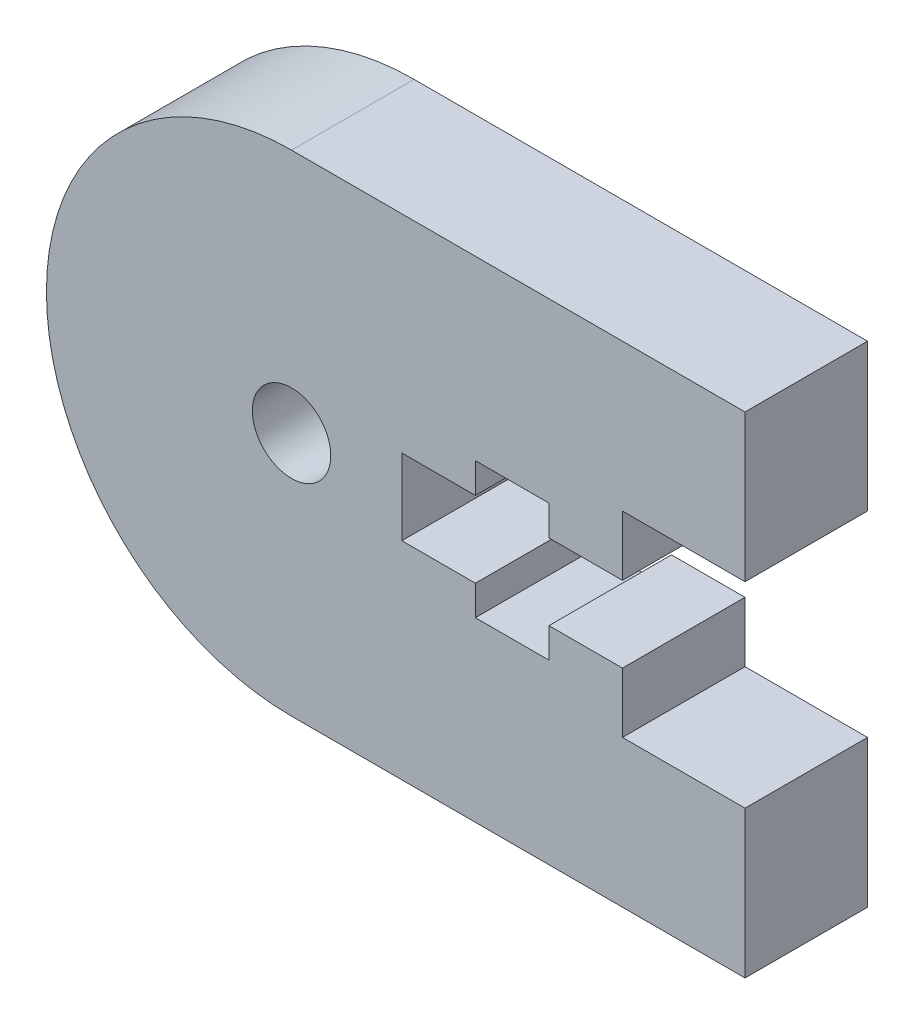
SolidWorks part; units mm, degrees
ref_plane "Plan de face" through (0, 0, 0) normal (0, 0, 1) x (1, 0, 0)
ref_plane "Plan de dessus" through (0, 0, 0) normal (0, 1, 0) x (1, 0, 0)
ref_plane "Plan de droite" through (0, 0, 0) normal (1, 0, 0) x (0, 0, -1)
ref_plane "Plan1" through (0, 0, 0) normal (0, 0, -1) x (-1, 0, 0)
sketch "Esquisse1" plane through (0, 0, 0) normal (0, 0, -1) x (-1, 0, 0)
  line L0 (-17, 10) -> (-17, -10)
  line L1 (-17, -10) -> (1.5, -10)
  line L2 (1.5, 10) -> (-17, 10)
  arc A0 (1.5, -10) -> (1.5, 10) centre (1.5, 0) ccw
  dimension "D1" = 20
extrude "Boss.-Extru.1" add sketch "Esquisse1" against normal blind 5
sketch "Esquisse2" plane through (0, 0, 5) normal (0, 0, 1) x (1, 0, 0)
  line L0 (17, -4) -> (17, 4)
  line L1 (17, 4) -> (12, 4)
  line L2 (12, 4) -> (12, -4)
  line L3 (12, -4) -> (17, -4)
extrude "Enlèv. mat.-Extru.1" cut sketch "Esquisse2" against normal through all
sketch "Esquisse3" plane through (0, 0, 5) normal (0, 0, 1) x (1, 0, 0)
  line L0 (-10.1603, -5) -> (7, -5)
  line L1 (7, -5) -> (7, 5)
  line L2 (7, 5) -> (-10.1603, 5)
  arc A0 (-10.1603, 5) -> (-10.1603, -5) centre (-1.5, 0) ccw
extrude "Enlèv. mat.-Extru.2" cut sketch "Esquisse3" against normal blind 2.5
hole_wizard "Diamètre du perçage Ø2.5 (2.5)2" positions "Esquisse7" profile "Esquisse6" hole size "Ø2.5" standard "Ansi Metric"
sketch "Esquisse7" plane through (0, 0, 2.5) normal (0, 0, 1) x (1, 0, 0)
  point P0 (-1.5, 0)
sketch "Esquisse6" plane through (-1.5, 0, 2.5) normal (1, 0, 0) x (0, -1, 0)
  line L0 (0, 0) -> (0, 2.5)
  line L1 (0, 2.5) -> (1.25, 2.5)
  line L2 (1.25, 2.5) -> (1.25, 0)
  line L5 (1.25, 0) -> (0, 0)
  line L11 (0, -6.35) -> (0, 107.95) construction
  dimension "Diamètre du perçage jusqu'au prochain" = 2.5
  dimension "Profondeur du perçage jusqu'au prochain" = 2.5
sketch "Esquisse9" plane through (0, 0, 5) normal (0, 0, 1) x (1, 0, 0)
  line L0 (-1.5, 10) -> (17, 10) construction
  line L1 (-1.5, -10) -> (7.75, -10)
  line L2 (-1.5, -10) -> (-1.5, 10)
  line L3 (-1.5, 10) -> (7.75, 10)
  line L4 (7.75, -10) -> (7.75, 10)
  arc A0 (-1.5, -10) -> (-1.5, 10) centre (-1.5, 0) cw
  line M2 (-10.1603, 5) -> (7, 5)
  line M3 (7, 5) -> (7, -5)
  line M4 (7, -5) -> (-10.1603, -5)
extrude "Boss.-Extru.2" add sketch "Esquisse9" against normal blind 5 contours A0 L2 M4 M2 | L2 M4 M3 M2 region at (-6.2912, 0, 5) region at (2.75, 0, 5)
sketch "Esquisse10" plane through (0, 0, 5) normal (0, 0, 1) x (1, 0, 0)
  line L0 (12, 4) -> (12, -4) construction
  line L1 (17, 4) -> (12, 4) construction
  line L2 (12, -1.55) -> (3, -1.55)
  line L3 (12, -1.55) -> (12, 1.55)
  line L4 (12, 1.55) -> (3, 1.55)
  line L5 (3, -1.55) -> (3, 1.55)
  line L6 (6, -2.77) -> (9, -2.77)
  line L7 (6, -2.77) -> (6, 2.78)
  line L8 (6, 2.78) -> (9, 2.78)
  line L9 (9, -2.77) -> (9, 2.78)
  line L10 (-1.5, 10) -> (-1.5, -10) construction
  circle A0 centre (-1.5, 0) radius 1.6
  line M12 (12, -4) -> (12, 4)
  dimension "D8" = 3.2
  dimension "D1" = 3
  dimension "D2" = 3
  dimension "D3" = 2.45
  dimension "D4" = 3.1
  dimension "D5" = 5.55
  dimension "D6" = 1.23
  dimension "D7" = 3
extrude "Enlèv. mat.-Extru.3" cut sketch "Esquisse10" against normal through all contours L2 L9 L4 L7 | L6 L9 L2 L7 | L2 L7 L4 L5 | L4 L9 L8 L7 | L9 L2 L4 M12 | L10 A0 | A0 L10 region at (10.5, 0, 5) region at (7.5, -2.16, 5) region at (7.5, 0, 5) region at (4.5, 0, 5) region at (7.5, 2.165, 5) region at (-0.8209, 0, 5) region at (-2.1791, 0, 5)
